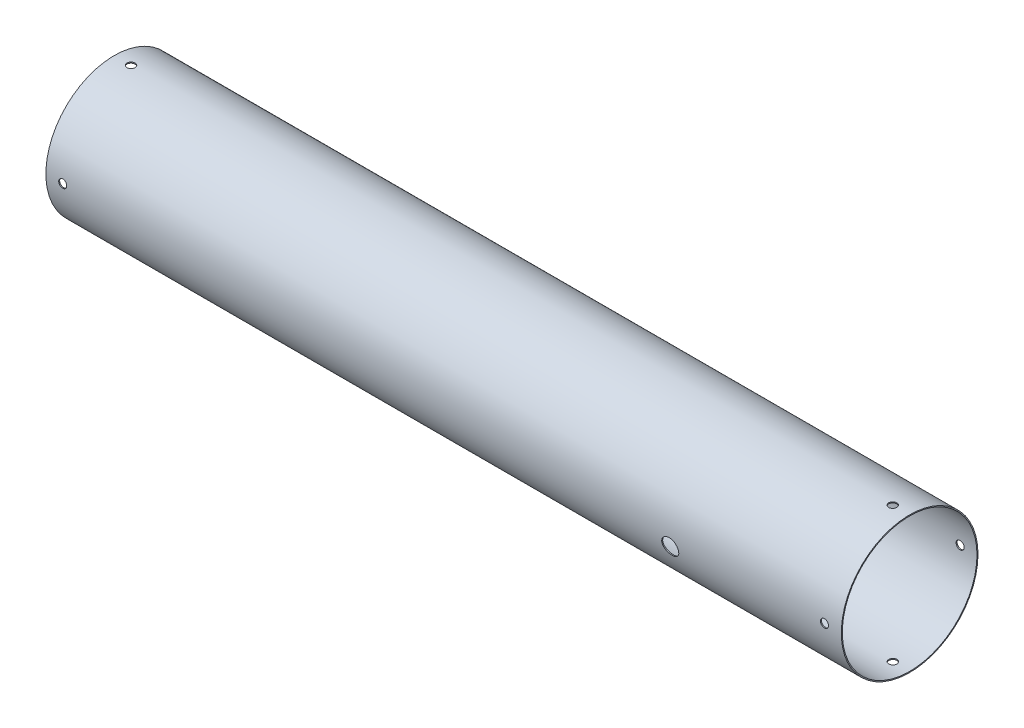
SolidWorks part; units mm, degrees
ref_plane "Front Plane" through (0, 0, 0) normal (0, 0, 1) x (1, 0, 0)
ref_plane "Top Plane" through (0, 0, 0) normal (0, 1, 0) x (1, 0, 0)
ref_plane "Right Plane" through (0, 0, 0) normal (1, 0, 0) x (0, 0, -1)
sketch "Sketch1" plane through (0, 0, 0) normal (1, 0, 0) x (0, 0, -1)
  circle A0 centre (0, 0) radius 51.562
  circle A1 centre (0, 0) radius 50.8
  dimension "D1" = 103.124
  dimension "D2" = 101.6
extrude "Boss-Extrude1" add sketch "Sketch1" along normal mid plane 600
sketch "Sketch3" plane through (0, 0, 0) normal (0, 0, 1) x (1, 0, 0)
  line L0 (300, -51.562) -> (300, 51.562) construction
  circle A1 centre (170.18, -8.89) radius 6.35
  point P4 (165.1, -14.856)
  dimension "D2" = 12.7
  dimension "D3" = 8.89
  dimension "D1" = 129.82
extrude "Cut-Extrude1" cut sketch "Sketch3" against normal through all both and the other way through all
sketch "Sketch4" plane through (0, 0, 0) normal (0, 0, 1) x (1, 0, 0)
  line L0 (300, -51.562) -> (300, 51.562) construction
  line L1 (-300, 51.562) -> (-300, -51.562) construction
  circle A0 centre (287.3, 0) radius 3.048
  circle A1 centre (-287.3, 0) radius 3.048
  dimension "D2" = 6.096
  dimension "D3" = 6.096
  dimension "D1" = 12.7
  dimension "D4" = 12.7
extrude "Cut-Extrude2" cut sketch "Sketch4" against normal through all both and the other way through all contours A1 | A0 region at (-287.3, 0, 0)
pattern_circular "CirPattern1" count 2 every 90 about axis through (300, 0, 0) along (-1, 0, 0) of "Cut-Extrude2"
